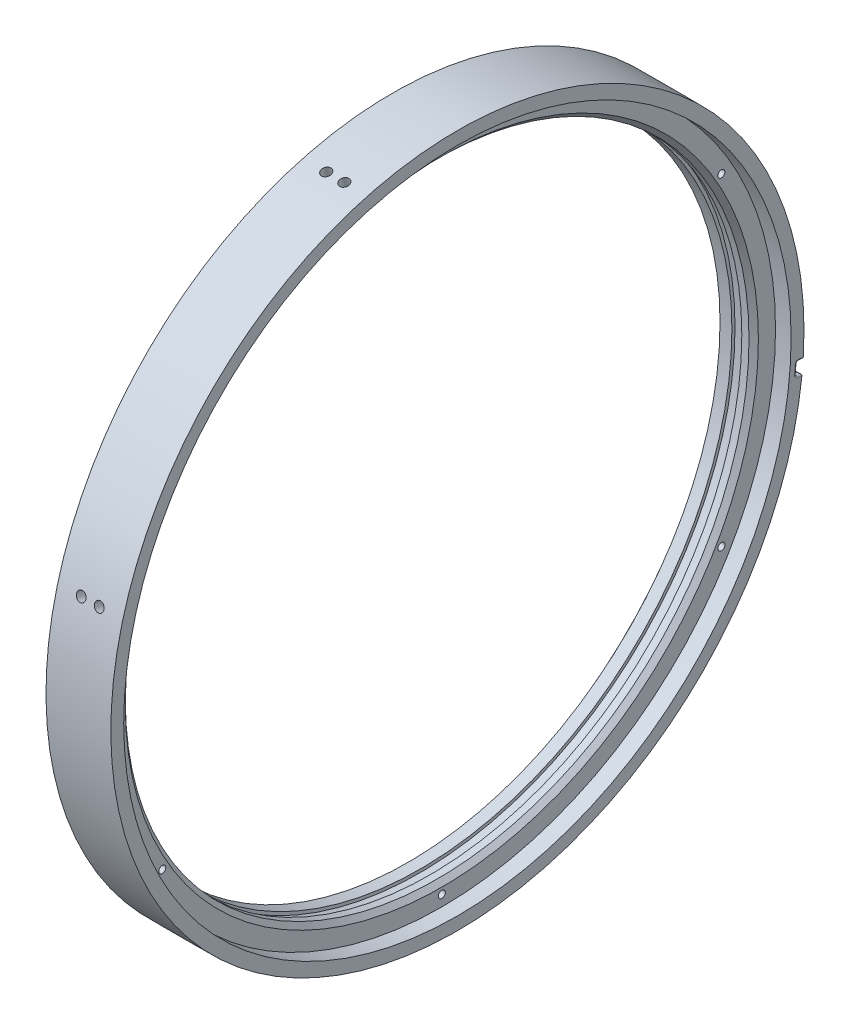
SolidWorks part; units mm, degrees
material "Delrin 2700 NC010, Low Viscosity Acetal Copolymer (SS)"
ref_plane "Front Plane" through (0, 0, 0) normal (0, 0, 1) x (1, 0, 0)
ref_plane "Top Plane" through (0, 0, 0) normal (0, 1, 0) x (1, 0, 0)
ref_plane "Right Plane" through (0, 0, 0) normal (1, 0, 0) x (0, 0, -1)
sketch "Sketch3" plane through (0, 0, 0) normal (0, 1, 0) x (1, 0, 0)
  line L0 (0, 0) -> (0, -111.125) construction
  line L1 (-10.3985, -111.125) -> (10.3986, -111.125)
  line L2 (10.3986, -111.125) -> (10.3986, -107)
  line L3 (10.3986, -107) -> (5.3986, -107)
  line L4 (5.3986, -107) -> (5.3986, -100)
  line L5 (5.3986, -100) -> (1.5875, -100)
  line L6 (1.5875, -100) -> (1.5875, -101)
  line L7 (1.5875, -101) -> (-1.5875, -101)
  line L8 (-10.3985, -111.125) -> (-10.3985, -107)
  line L9 (-10.3985, -107) -> (-5.3985, -107)
  line L10 (-5.3985, -107) -> (-5.3985, -100)
  line L11 (-5.3985, -100) -> (-1.5875, -100)
  line L12 (-1.5875, -100) -> (-1.5875, -101)
  line L13 (0, 0) -> (-91.3824, 0) construction
  point P16 (0, -101)
  dimension "D1" = 111.125
  dimension "D2" = 5.3986
  dimension "D3" = 100
  dimension "D4" = 5
  dimension "D5" = 7
  dimension "D6" = 1.5875
  dimension "D7" = 1
revolve "Revolve1" add sketch "Sketch3" angle 360 about L13
chamfer "Chamfer1" distance 1.5 angle 45 1 edges at (5.3986, 0, -100)
sketch "Sketch4" plane through (5.3986, 0, 0) normal (1, 0, 0) x (0, 0, -1)
  circle A0 centre (0, 0) radius 103.5 construction
  circle A1 centre (0, 0) radius 107
  circle A2 centre (0, 0) radius 107
  point P1 (0, -103.5)
  point P5 (-89.6336, -51.75)
  point P8 (-89.6336, 51.75)
  point P9 (0, 103.5)
  point P10 (89.6336, 51.75)
  point P11 (89.6336, -51.75)
  dimension "D2" = 207
  dimension "D1" = 0
  dimension "D3" = 6
hole_wizard "Tap Drill for #4-40 Tap1" positions "3DSketch1" profile "Sketch5" hole size "#4-40" standard "Ansi Inch"
sketch3d "3DSketch1"
  point P0 (5.3986, -103.5, 0)
  point P3 (5.3986, -51.75, 89.6336)
  point P6 (5.3986, -51.75, -89.6336)
  point P9 (5.3986, 51.75, -89.6336)
  point P12 (5.3986, 103.5, 0)
  point P15 (5.3986, 51.75, 89.6336)
sketch "Sketch5" plane through (5.3986, -103.5, 0) normal (0, 1, 0) x (0, 0, -1)
  line L0 (0, 0) -> (0, 9.5692)
  line L1 (0, 9.5692) -> (1.1303, 8.89)
  line L2 (1.1303, 8.89) -> (1.1303, 0)
  line L5 (1.1303, 0) -> (0, 0)
  line L10 (0, 9.5692) -> (-1.1303, 8.89) construction
  line L11 (0, -6.35) -> (0, 107.95) construction
  dimension "Hole Dia." = 2.2606
  dimension "Hole Depth" = 8.89
  dimension "Drill Angle" = 118
sketch "Sketch6" plane through (-5.3985, 0, 0) normal (-1, 0, 0) x (0, 0, 1)
  line L0 (0, 0) -> (0, -103.5) construction
  line L1 (0, 0) -> (51.75, -89.6336) construction
  line L2 (0, 0) -> (-51.75, -89.6336) construction
  line L3 (0, 0) -> (-103.5, 0) construction
  line L4 (0, 0) -> (-51.75, 89.6336) construction
  line L5 (0, 0) -> (51.75, 89.6336) construction
  line L6 (0, 0) -> (103.5, 0) construction
  circle A0 centre (0, 0) radius 103.5
  circle A1 centre (0, 0) radius 107
  circle A2 centre (0, 0) radius 107
  dimension "D2" = 207
  dimension "D3" = 30
  dimension "D1" = 0
  dimension "D4" = 6
hole_wizard "Tap Drill for #4-40 Tap2" positions "3DSketch2" profile "Sketch7" hole size "#4-40" standard "Ansi Inch"
sketch3d "3DSketch2"
  point P0 (-5.3985, -89.6336, 51.75)
  point P3 (-5.3985, 0, 103.5)
  point P6 (-5.3985, 89.6336, 51.75)
  point P9 (-5.3985, 89.6336, -51.75)
  point P12 (-5.3985, 0, -103.5)
  point P15 (-5.3985, -89.6336, -51.75)
sketch "Sketch7" plane through (-5.3985, -89.6336, 51.75) normal (0, 1, 0) x (0, 0, 1)
  line L0 (0, 0) -> (0, 9.5692)
  line L1 (0, 9.5692) -> (1.1303, 8.89)
  line L2 (1.1303, 8.89) -> (1.1303, 0)
  line L5 (1.1303, 0) -> (0, 0)
  line L10 (0, 9.5692) -> (-1.1303, 8.89) construction
  line L11 (0, -6.35) -> (0, 107.95) construction
  dimension "Hole Dia." = 2.2606
  dimension "Hole Depth" = 8.89
  dimension "Drill Angle" = 118
ref_plane "Plane1" through (0, 107.3385, 28.7613) normal (0, 0.9659, 0.2588) x (-1, 0, 0)
sketch "Sketch8" plane through (0, 107.3385, 28.7613) normal (0, 0.9659, 0.2588) x (-1, 0, 0)
  line L0 (0, 0) -> (-10.3986, 0) construction
  line L1 (-10.3986, 111.125) -> (-10.3986, -111.125) construction
  line L2 (0, 0) -> (10.3985, 0) construction
  line L3 (10.3985, -111.125) -> (10.3985, 111.125) construction
  circle A0 centre (-2.8986, 0) radius 1.524
  circle A1 centre (2.8985, 0) radius 1.524
  dimension "D3" = 3.048
  dimension "D4" = 7.5
  dimension "D1" = 3.048
  dimension "D2" = 7.5
extrude "Cut-Extrude1" cut sketch "Sketch8" against normal blind 8.89
ref_axis "Axis1" through (-10.3985, 0, 0) along (1, 0, 0)
pattern_circular "CirPattern1" count 6 over 360 about axis through (-10.3985, 0, 0) along (1, 0, 0) of "Cut-Extrude1"
ref_axis "Axis2" through (-2.8985, 98.0154, 26.2631) along (0, 0.9659, 0.2588)
ref_axis "Axis3" through (2.8986, 98.0154, 26.2631) along (0, 0.9659, 0.2588)
sketch "Sketch10" plane through (0, 107.3385, 28.7613) normal (0, 0.9659, 0.2588) x (-1, 0, 0)
  line L0 (-10.3986, 0) -> (12.3268, 0) construction
  line L1 (-10.3986, 111.125) -> (-10.3986, -111.125) construction
  line L2 (10.3985, 0) -> (-10.3986, 0) construction
  line L3 (10.3985, -111.125) -> (10.3985, 111.125) construction
  line L4 (-10.3986, 0) -> (10.3985, 0)
  line L5 (-10.3986, -11) -> (-10.3986, 11)
  line L6 (-10.3986, 11) -> (10.3985, 11)
  line L7 (10.3985, -11) -> (10.3985, 11)
  line L8 (-10.3986, -11) -> (10.3985, -11)
  dimension "D1" = 11
extrude "Cut-Extrude2" [suppressed] cut sketch "Sketch10" against normal blind 6 contours L5 L8 L7 L4 | L4 L7 L6 L5
sketch "Sketch11" plane through (10.3986, 0, 0) normal (1, 0, 0) x (0, 0, -1)
  line L0 (0, 0) -> (111.125, 0) construction
  line L1 (0, 0) -> (110.7021, -9.6852) construction
  circle A2 centre (0, 0) radius 111.125 construction
  dimension "D1" = 5
ref_plane "Plane2" through (10.3986, -9.6852, -110.7021) normal (0, -0.0872, -0.9962) x (-1, 0, 0)
sketch "Sketch12" plane through (10.3986, -9.6852, -110.7021) normal (0, -0.0872, -0.9962) x (-1, 0, 0)
  line L0 (0, 111.125) -> (0, -111.125) construction
  line L1 (0, 0) -> (20.7971, 0)
  line L2 (0, -2) -> (0, 2)
  line L3 (0, 2) -> (20.7971, 2)
  line L4 (20.7971, -2) -> (20.7971, 2)
  line L5 (20.7971, -111.125) -> (20.7971, 111.125) construction
  line L6 (0, -2) -> (20.7971, -2)
  dimension "D1" = 2
extrude "Cut-Extrude3" cut sketch "Sketch12" against normal blind 2 contours L1 L4 L3 L2 | L2 L6 L4 L1 region at (0, -8.689, -110.7893) region at (0, -10.6814, -110.615)
fillet "Fillet1" radius 0.5 10 edges at (10.3986, -7.6049, -109.8713) (-10.3985, -7.6049, -109.8713) (10.3986, -9.5109, -108.7097) (-10.3985, -9.5109, -108.7097) (0, -11.676, -110.5099) (10.3986, -11.5896, -109.5227) (0, -11.5033, -108.5354) (-10.3985, -11.5896, -109.5227) (0, -7.6912, -110.8585) (0, -7.5185, -108.8841)
sketch "Sketch13" plane through (-5.3985, 0, 0) normal (-1, 0, 0) x (0, 0, 1)
  line L0 (0, 0) -> (-51.75, -89.6336) construction
  line L1 (0, 0) -> (-49.4071, -94.9102)
  line L2 (0, 0) -> (-57.4911, -90.2429)
  line L9 (0, 0) -> (-106.8982, 4.6673)
  line L10 (0, 0) -> (-106.8982, -4.6673)
  line L11 (0, 0) -> (-49.4071, 94.9102)
  line L12 (0, 0) -> (-57.4911, 90.2429)
  line L13 (0, 0) -> (57.4911, 90.2429)
  line L14 (0, 0) -> (49.4071, 94.9102)
  line L15 (0, 0) -> (106.8982, -4.6673)
  line L16 (0, 0) -> (106.8982, 4.6673)
  line L17 (0, 0) -> (49.4071, -94.9102)
  line L18 (0, 0) -> (57.4911, -90.2429)
  circle A0 centre (0, 0) radius 100 construction
  circle A1 centre (0, 0) radius 107
  circle A2 centre (0, 0) radius 107
  circle A3 centre (0, 0) radius 100
  dimension "D2" = 2.5
  dimension "D3" = 2.5
  dimension "D1" = 0
  dimension "D4" = 6
